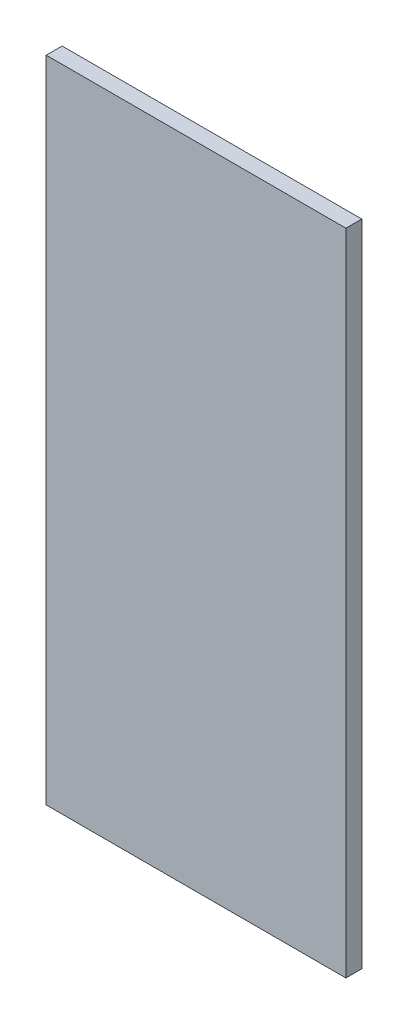
SolidWorks part; units mm, degrees
material "Custom Plastic"
ref_plane "X-Y Datum" through (0, 0, 0) normal (0, 0, 1) x (1, 0, 0)
ref_plane "X-Z Datum" through (0, 0, 0) normal (0, 1, 0) x (1, 0, 0)
ref_plane "Y-Z Datum" through (0, 0, 0) normal (1, 0, 0) x (0, 0, -1)
sketch "Sketch1" plane through (0, 0, 0) normal (0, 0, 1) x (1, 0, 0)
  line L1 (-30, -65) -> (30, -65)
  line L2 (-30, -65) -> (-30, 65)
  line L3 (-30, 65) -> (30, 65)
  line L4 (30, -65) -> (30, 65)
  line L5 (-30, -65) -> (30, 65) construction
  line L6 (-30, 65) -> (30, -65) construction
  point P0 (0, 0)
  dimension "D1" = 130
  dimension "D2" = 60
base flange "Base-Flange1" sketch "Sketch1" thickness 3.175 reverse thickness direction no parameters "D1"=10
sketch "Bend-Lines1" [suppressed] plane through (0, 0, 0) normal (0, 1, 0) x (1, 0, 0)
sketch "Bounding-Box1" [suppressed] plane through (0, 0, 0) normal (0, 1, 0) x (1, 0, 0)
sheet metal parameters "Sheet-Metal1" thickness 3.175 parameters "D1"=10
flat pattern "Flat-Pattern1" [suppressed]
sketch "Bend-Lines2" plane through (0, 0, 0) normal (0, 1, 0) x (1, 0, 0)
sketch3d "Bounding-Box2" [suppressed]
  line L0 (-30, 65, 0) -> (-30, -65, 0) construction
  line L1 (30, 65, 0) -> (30, -65, 0) construction
  line L2 (-30, 65, 0) -> (30, 65, 0) construction
  line L3 (-30, -65, 0) -> (30, -65, 0) construction
